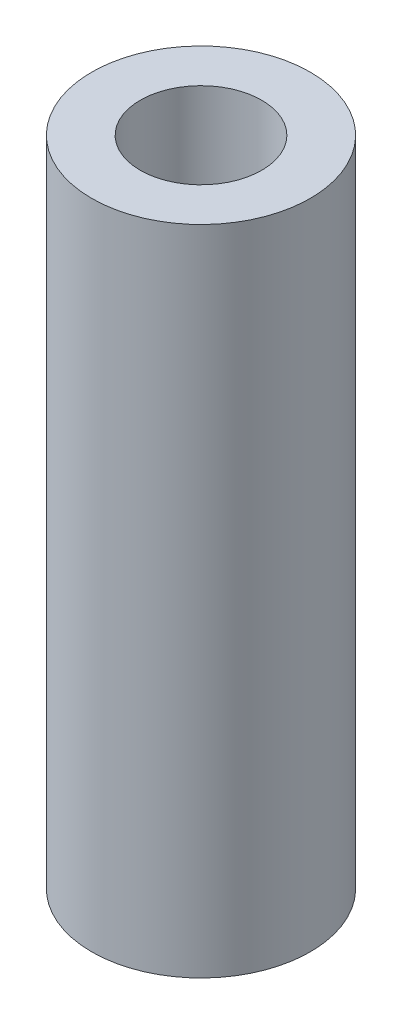
SolidWorks part; units mm, degrees
material "EPDM"
ref_plane "Płaszczyzna przednia" through (0, 0, 0) normal (0, 0, 1) x (1, 0, 0)
ref_plane "Płaszczyzna górna" through (0, 0, 0) normal (0, 1, 0) x (1, 0, 0)
ref_plane "Płaszczyzna prawa" through (0, 0, 0) normal (1, 0, 0) x (0, 0, -1)
sketch "Szkic1" plane through (0, 0, 0) normal (0, 0, 1) x (1, 0, 0)
  line L0 (0, 344.7443) -> (0, -336.9732) construction
  line L1 (35, 188) -> (63, 188)
  line L2 (35, 188) -> (35, -188)
  line L3 (35, -188) -> (63, -188)
  line L4 (63, 188) -> (63, -188)
  point P4 (35, 0)
  dimension "D1" = 63
  dimension "D2" = 35
  dimension "D3" = 376
revolve "Obrót1" add sketch "Szkic1" angle 360 about L0
